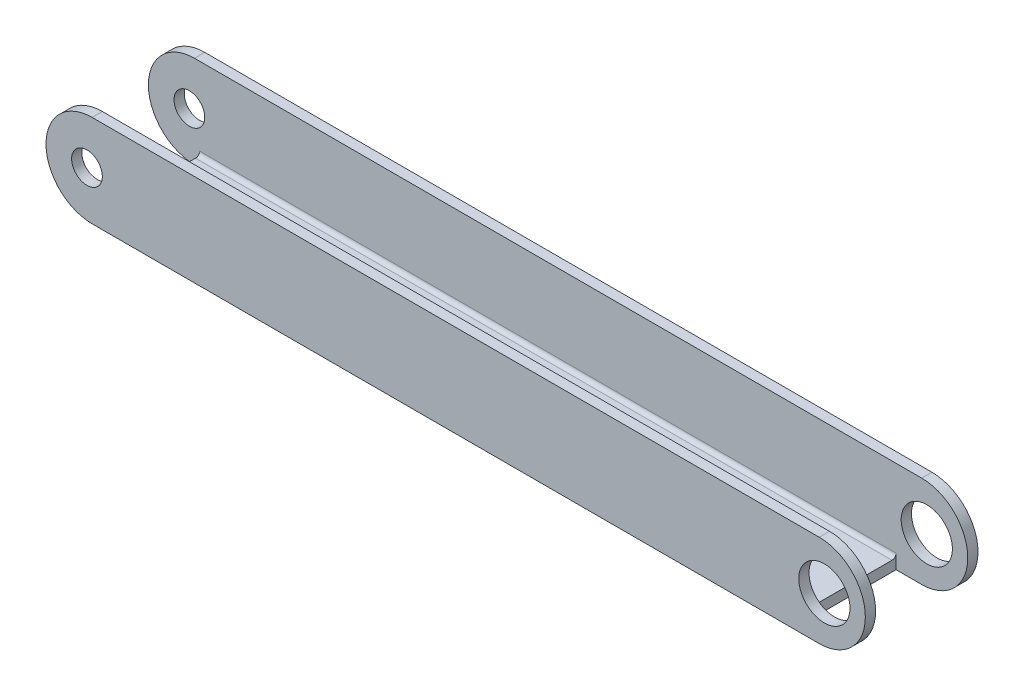
SolidWorks part; units mm, degrees
ref_plane "Front Plane" through (0, 0, 0) normal (0, 0, 1) x (1, 0, 0)
ref_plane "Top Plane" through (0, 0, 0) normal (0, 1, 0) x (1, 0, 0)
ref_plane "Right Plane" through (0, 0, 0) normal (1, 0, 0) x (0, 0, -1)
sketch "Sketch1" plane through (0, 0, 0) normal (1, 0, 0) x (0, 0, -1)
  line L0 (-22.5, 40) -> (-22.5, 0)
  line L1 (-22.5, 0) -> (22.5, 0)
  line L2 (22.5, 0) -> (22.5, 40)
  dimension "D1" = 45
  dimension "D2" = 40
extrude "Extrude-Thin1" add sketch "Sketch1" along normal mid plane 400 thin thin type one direction wall 5
sketch "Sketch3" plane through (0, 0, 0) normal (0, 0, 1) x (1, 0, 0)
  line L0 (0, 0) -> (0, 115.3057) construction
  line L1 (-200, 40) -> (-200, -5) construction
  line L2 (-200, 17.5) -> (-180, 17.5) construction
  circle A0 centre (-180, 17.5) radius 7.5
  circle A1 centre (180, 17.5) radius 12.5
  dimension "D2" = 15
  dimension "D3" = 25
  dimension "D1" = 20
extrude "Cut-Extrude1" cut sketch "Sketch3" against normal through all both and the other way through all
sketch "Sketch4" plane through (0, -5, 0) normal (0, 1, 0) x (1, 0, 0)
  line L0 (200, -22.5) -> (200, 22.5)
  line L1 (200, 22.5) -> (165, 22.5)
  line L3 (165, 22.5) -> (165, -22.5)
  line L4 (200, -22.5) -> (-200, -22.5) construction
  line L5 (165, -22.5) -> (200, -22.5)
  line L6 (200, 22.5) -> (-200, 22.5) construction
  dimension "D1" = 35
extrude "Cut-Extrude2" cut sketch "Sketch4" along normal through all
sketch "Sketch5" plane through (0, -5, 0) normal (0, 1, 0) x (1, 0, 0)
  line L0 (-200, 22.5) -> (-200, -22.5)
  line L1 (-200, -22.5) -> (-175, -22.5)
  line L2 (165, -22.5) -> (-200, -22.5) construction
  line L3 (-175, -22.5) -> (-175, 22.5)
  line L4 (165, 22.5) -> (-200, 22.5) construction
  line L5 (-175, 22.5) -> (-200, 22.5)
  dimension "D1" = 25
extrude "Cut-Extrude3" cut sketch "Sketch5" along normal through all
fillet "Fillet1" 2 edges at (-200, 40, -25) (-200, -5, -25) type full round first side face at (0, 40, -25) second side face at (-1.6667, -5, 0) middle face at (-200, 17.5, -25)
fillet "Fillet2" 2 edges at (-200, 40, 25) (-200, -5, 25) type full round first side face at (0, 40, 25) second side face at (2.0833, -5, 0) middle face at (-200, 17.5, 25)
fillet "Fillet3" radius 2 2 edges at (-5, 0, 22.5) (-5, 0, -22.5)
fillet "Fillet4" 2 edges at (200, 40, -25) (200, -5, -25) type full round first side face at (11.25, 40, -25) second side face at (5.8333, -5, 0) middle face at (200, 17.5, -25)
fillet "Fillet5" 2 edges at (200, 40, 25) (200, -5, 25) type full round first side face at (11.25, 40, 25) second side face at (2.0833, -5, 0) middle face at (200, 17.5, 25)
